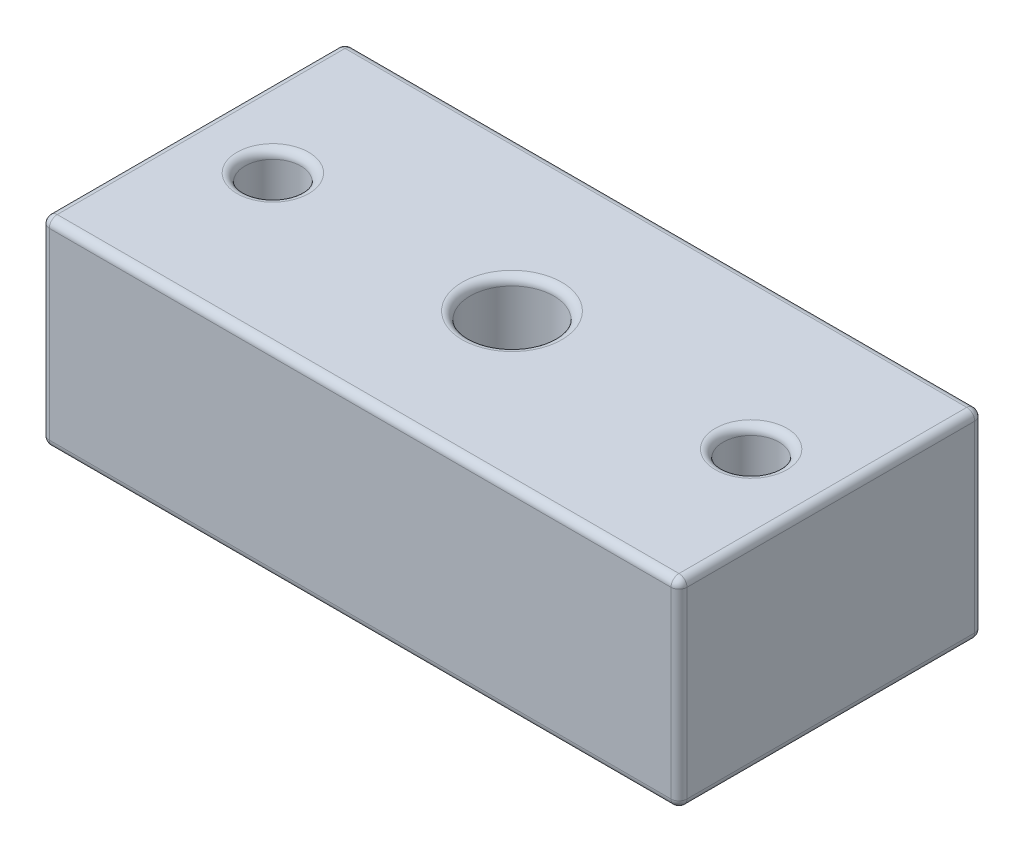
SolidWorks part; units mm, degrees
other "Markup1"
sketch "Sketch2" plane through (0, -5, 0) normal (-0.0836, -0.3487, -0.9335) x (0.9823, 0.1286, -0.136)
ref_plane "Front Plane" through (0, 0, 0) normal (0, 0, 1) x (1, 0, 0)
ref_plane "Top Plane" through (0, 0, 0) normal (0, 1, 0) x (1, 0, 0)
ref_plane "Right Plane" through (0, 0, 0) normal (1, 0, 0) x (0, 0, -1)
sketch "Sketch1" plane through (0, 0, 0) normal (0, 1, 0) x (1, 0, 0)
  line L1 (0, 0) -> (80, 0)
  line L2 (0, 0) -> (0, -38.1)
  line L3 (0, -38.1) -> (80, -38.1)
  line L4 (80, 0) -> (80, -38.1)
  circle A0 centre (40, -19.05) radius 10.5
  circle A1 centre (10, -19.05) radius 3.5
  circle A2 centre (70, -19.05) radius 3.5
  circle A3 centre (10, -19.05) radius 5
  circle A4 centre (70, -19.05) radius 5
  circle A5 centre (40, -19.05) radius 5.25
  dimension "D6" = 21
  dimension "D7" = 7
  dimension "D9" = 10
  dimension "D12" = 10.5
  dimension "D1" = 80
  dimension "D2" = 38.1
  dimension "D3" = 19.05
  dimension "D4" = 10
  dimension "D5" = 60
  dimension "D10" = 0
  dimension "D11" = 40
  dimension "D8" = 0
extrude "Boss-Extrude1" add sketch "Sketch1" along normal blind 20 contours L4 L1 L2 L3 A4 A3 A0 | A3 A1 | A4 A2 region at (40, 0, 0.8861) region at (5.1414, 0, 19.05) region at (65.1414, 0, 19.05)
extrude "Boss-Extrude2" add sketch "Sketch1<4>" against normal blind 10 from surface contours A0 A5 region at (29.797, 0, 19.05) starting at face at (40, 20, 29.55)
sketch "Sketch1<4>" plane through (0, 0, 0) normal (0, 1, 0) x (1, 0, 0) same geometry as "Sketch1"
extrude "Boss-Extrude4" add sketch "Sketch1<6>" against normal blind 5 contours L4 L1 L2 L3 A4 A3 A0 | A4 A2 | A3 A1 region at (40, 0, 0.8861) region at (5.1414, 0, 19.05) region at (65.1414, 0, 19.05)
sketch "Sketch1<6>" plane through (0, 0, 0) normal (0, 1, 0) x (1, 0, 0) same geometry as "Sketch1"
fillet "Fillet2" radius 1 16 edges at (40, -5, 29.55) (40, -5, 38.1) (0, 7.5, 38.1) (0, -5, 19.05) (0, 7.5, 0) (40, -5, 0) (80, 7.5, 0) (80, -5, 19.05) (80, 7.5, 38.1) (40, 20, 24.3) (70, 20, 22.55) (10, 20, 22.55) (40, 20, 38.1) (0, 20, 19.05) (40, 20, 0) (80, 20, 19.05)
sketch "Sketch3" plane through (0, 0, 0) normal (0, 0, 1) x (1, 0, 0)
  line L0 (36.5, 2) -> (36.5, 5.5)
  line L1 (43.5, 2) -> (43.5, 5.5)
  line L2 (79, -4) -> (1, -4) construction
  line L3 (79, 19) -> (79, -4) construction
  circle A0 centre (40, 2) radius 3.5
  circle A1 centre (40, 5.5) radius 3.5
  dimension "D1" = 7
  dimension "D2" = 3.5
  dimension "D3" = 6
  dimension "D4" = 39
extrude "Cut-Extrude1" cut sketch "Sketch3" along normal blind 10 contours A1 A0 | A0 A1 | A1 A0 | A1 A0 L1 | A1 L0 A0 region at (40, 0.8764, 0) region at (36.6389, 3.75, 0) region at (40, 6.6236, 0) region at (43.3611, 3.75, 0) region at (40, 3.75, 0)
equation "\"D3@Sketch1\"=\"D2@Sketch1\"/2"
equation "\"D4@Sketch1\"=(\"D1@Sketch1\"-\"D5@Sketch1\")/2"
